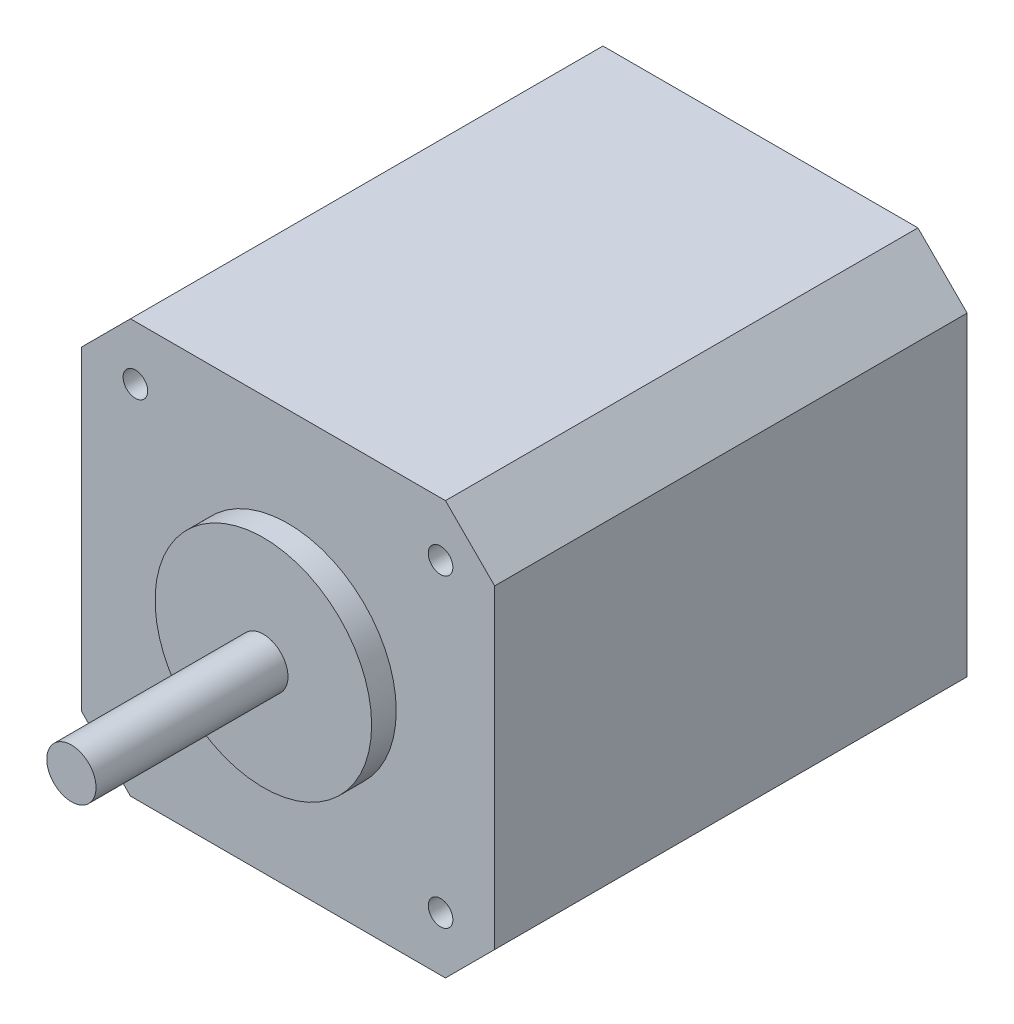
SolidWorks part; units mm, degrees
ref_plane "前视基准面" through (0, 0, 0) normal (0, 0, 1) x (1, 0, 0)
ref_plane "上视基准面" through (0, 0, 0) normal (0, 1, 0) x (1, 0, 0)
ref_plane "右视基准面" through (0, 0, 0) normal (1, 0, 0) x (0, 0, -1)
other "Configuration Table"
sketch "草图1" plane through (0, 0, 0) normal (0, 0, 1) x (1, 0, 0)
  line L0 (-21, 16) -> (-16, 21)
  line L1 (-16, 21) -> (16, 21)
  line L2 (-21, 16) -> (-21, -16)
  line L3 (-16, -21) -> (16, -21)
  line L4 (21, 16) -> (21, -16)
  line L5 (-21, 21) -> (21, -21) construction
  line L6 (-21, -21) -> (21, 21) construction
  line L7 (16, 21) -> (21, 16)
  line L8 (21, -16) -> (16, -21)
  line L9 (-21, -16) -> (-16, -21)
  point P0 (0, 0)
  dimension "D1" = 42
  dimension "D2" = 42
extrude "凸台-拉伸1" add sketch "草图1" along normal mid plane 48
sketch "草图2" plane through (0, 0, 24) normal (0, 0, 1) x (1, 0, 0)
  circle A0 centre (0, 0) radius 11
  circle A1 centre (0, 0) radius 2.5
  dimension "D1" = 22
  dimension "D2" = 5
extrude "凸台-拉伸2" add sketch "草图2" along normal blind 2.5
extrude "凸台-拉伸3" add sketch "草图2<2>" along normal blind 22 contours A1 region at (0, 0, 24)
sketch "草图2<2>" plane through (0, 0, 24) normal (0, 0, 1) x (1, 0, 0) same geometry as "草图2"
sketch "草图6" plane through (0, 0, 24) normal (0, 0, 1) x (1, 0, 0)
  line L0 (-27.8026, 0) -> (30.9689, 0) construction
  line L2 (0, 27.5213) -> (0, -27.7525) construction
  line L4 (0, 0) -> (-24.4897, 24.4897) construction
  line L6 (0, 0) -> (25.235, 25.235) construction
  point P0 (-15.5, 15.5)
  point P2 (15.5, 15.5)
  point P4 (15.5, -15.5)
  point P6 (-15.5, -15.5)
  dimension "D1" = 45
  dimension "D2" = 45
  dimension "D3" = 31
hole_wizard "M3 螺纹孔1" positions "草图6" profile "草图5" tap size "M3" standard "GB"
sketch "草图5" plane through (-15.5, 15.5, 24) normal (1, 0, 0) x (0, -1, 0)
  line L0 (0, 0) -> (0, 8.2511)
  line L1 (0, 8.2511) -> (1.25, 7.5)
  line L2 (1.25, 7.5) -> (1.25, 0)
  line L5 (1.25, 0) -> (0, 0)
  line L10 (0, 8.2511) -> (-1.25, 7.5) construction
  line L11 (0, -6.35) -> (0, 107.95) construction
  dimension "螺纹孔钻头直径" = 2.5
  dimension "螺纹孔钻头深度" = 7.5
  dimension "导头角度" = 118
cosmetic thread "孔螺纹线1" parameters "D1"=5, "D2"=3
cosmetic thread "孔螺纹线2" parameters "D1"=5, "D2"=3
cosmetic thread "孔螺纹线3" parameters "D1"=5, "D2"=3
cosmetic thread "孔螺纹线4" parameters "D1"=5, "D2"=3
